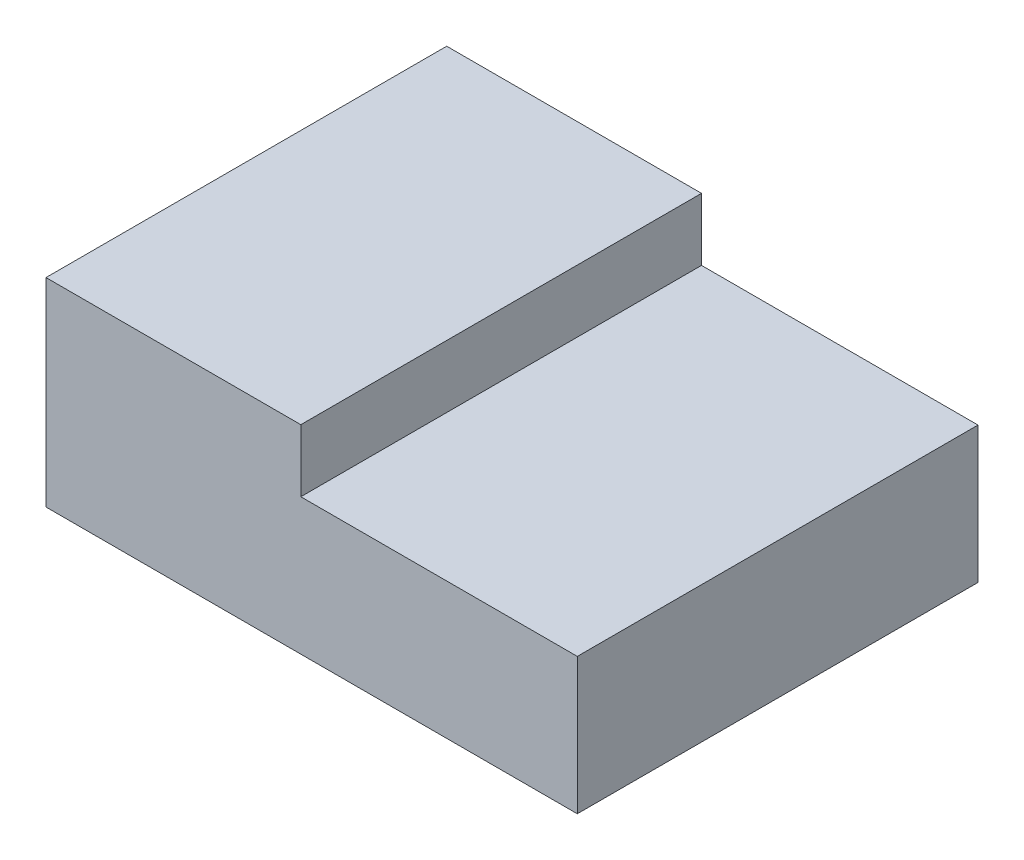
SolidWorks part; units mm, degrees
ref_plane "Front Plane" through (0, 0, 0) normal (0, 0, 1) x (1, 0, 0)
ref_plane "Top Plane" through (0, 0, 0) normal (0, 1, 0) x (1, 0, 0)
ref_plane "Right Plane" through (0, 0, 0) normal (1, 0, 0) x (0, 0, -1)
sketch "Sketch1" plane through (0, 0, 0) normal (0, 1, 0) x (1, 0, 0)
  line L0 (-0.85, 15.725) -> (-0.85, -15.725)
  line L1 (-20.85, 15.725) -> (20.85, 15.725)
  line L2 (-20.85, 15.725) -> (-20.85, -15.725)
  line L3 (-20.85, -15.725) -> (20.85, -15.725)
  line L4 (20.85, 15.725) -> (20.85, -15.725)
  line L5 (0, -15.725) -> (0, 15.725) construction
  line L6 (-20.85, 0) -> (20.85, 0) construction
  point P260 (0, 0)
  dimension "D1" = 41.7
  dimension "D2" = 31.45
  dimension "D3" = 20
extrude "Boss-Extrude1" add sketch "Sketch1" along normal blind 10.7 contours L4 L1 L0 L3 region at (10, 0, 0)
extrude "Boss-Extrude2" add sketch "Sketch1<4>" along normal blind 15.6 contours L2 L3 L0 L1 region at (-10.85, 0, 0)
sketch "Sketch1<4>" plane through (0, 0, 0) normal (0, 1, 0) x (1, 0, 0) same geometry as "Sketch1"
